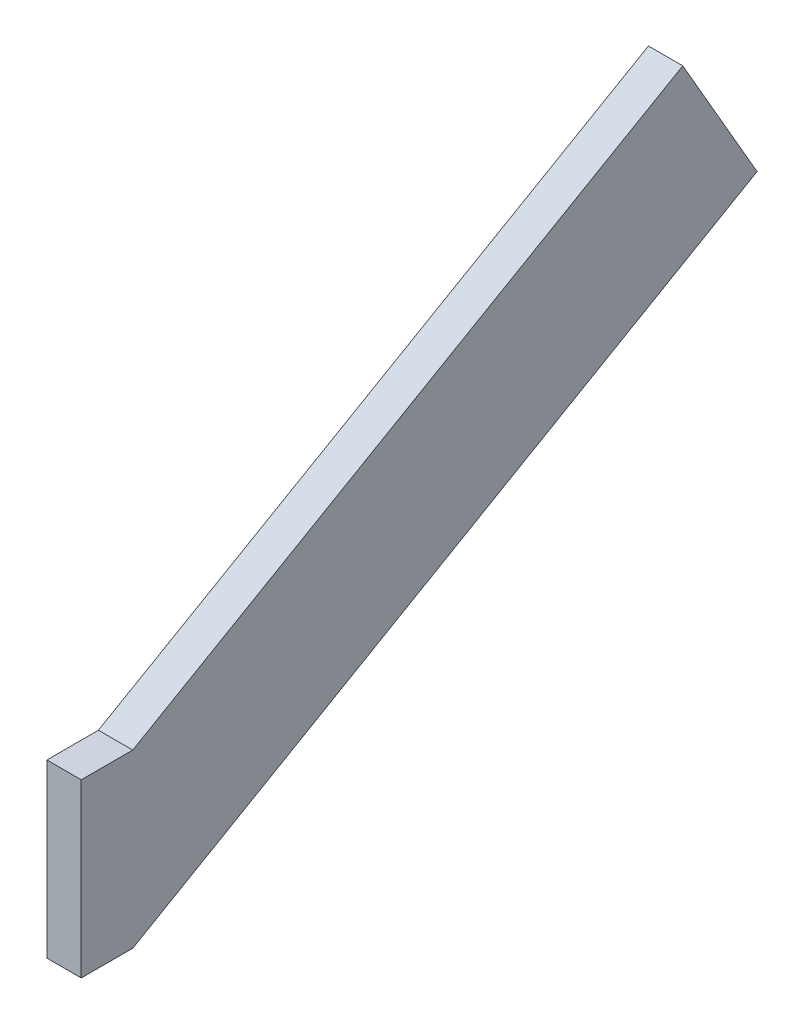
SolidWorks part; units mm, degrees
ref_plane "Alzado" through (0, 0, 0) normal (0, 0, 1) x (1, 0, 0)
ref_plane "Planta" through (0, 0, 0) normal (0, 1, 0) x (1, 0, 0)
ref_plane "Vista lateral" through (0, 0, 0) normal (1, 0, 0) x (0, 0, -1)
sketch "Croquis1" plane through (0, 0, 0) normal (1, 0, 0) x (0, 0, -1)
  line L0 (0, 0) -> (0, 50)
  line L1 (0, 50) -> (15, 50)
  line L2 (0, 0) -> (15, 0)
  line L3 (15, 0) -> (196.8653, 105)
  line L4 (15, 0) -> (40.1168, 0) construction
  line L5 (15, 50) -> (175.2147, 142.5)
  line L6 (175.2147, 142.5) -> (196.8653, 105)
  dimension "D1" = 50
  dimension "D2" = 15
  dimension "D3" = 30
  dimension "D4" = 210
  dimension "D5" = 185
extrude "Saliente-Extruir1" add sketch "Croquis1" along normal blind 10
